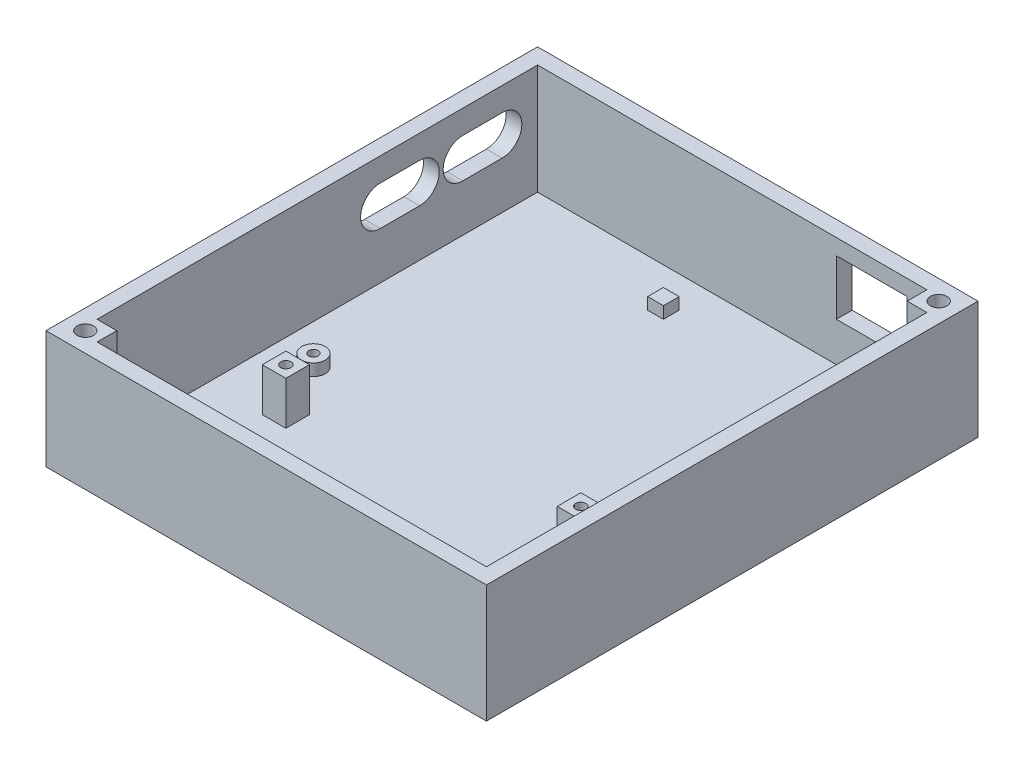
SolidWorks part; units mm, degrees
ref_plane "Front Plane" through (0, 0, 0) normal (0, 0, 1) x (1, 0, 0)
ref_plane "Top Plane" through (0, 0, 0) normal (0, 1, 0) x (1, 0, 0)
ref_plane "Right Plane" through (0, 0, 0) normal (1, 0, 0) x (0, 0, -1)
sketch "Sketch1" plane through (0, 0, 0) normal (0, 1, 0) x (1, 0, 0)
  line L1 (-56, -62.5) -> (56, -62.5)
  line L2 (-56, -62.5) -> (-56, 62.5)
  line L3 (-56, 62.5) -> (56, 62.5)
  line L4 (56, -62.5) -> (56, 62.5)
  line L5 (-56, -62.5) -> (56, 62.5) construction
  line L6 (-56, 62.5) -> (56, -62.5) construction
  point P0 (0, 0)
  dimension "D1" = 112
  dimension "D2" = 125
extrude "Boss-Extrude1" add sketch "Sketch1" along normal blind 2
sketch "Sketch2" plane through (0, 2, 0) normal (0, 1, 0) x (1, 0, 0)
  line L0 (-56, -62.5) -> (56, -62.5) construction
  line L1 (-12, 50.5) -> (-8, 50.5) construction
  line L2 (-12, 50.5) -> (-12, 46.5) construction
  line L3 (-12, 46.5) -> (-8, 46.5) construction
  line L4 (52, 53.5) -> (47, 53.5)
  line L5 (-8, 50.5) -> (-8, 46.5) construction
  line L6 (-56, 62.5) -> (-56, -62.5) construction
  line L7 (47, 53.5) -> (47, 58.5)
  line L8 (52, -58.5) -> (52, 58.5)
  line L9 (52, 58.5) -> (-52, 58.5)
  line L10 (-52, 58.5) -> (-52, -58.5)
  line L11 (-52, -58.5) -> (52, -58.5)
  line L12 (52, -58.5) -> (52, 53.5)
  line L13 (47, 58.5) -> (-52, 58.5)
  line L14 (-52, 58.5) -> (-52, -53.5)
  line L15 (-47, -58.5) -> (52, -58.5)
  line L16 (56, 62.5) -> (-56, 62.5) construction
  line L29 (-47, -58.5) -> (-47, -53.5)
  line L30 (-47, -53.5) -> (-52, -53.5)
  line L31 (56, -62.5) -> (56, 62.5) construction
  circle A0 centre (-42, -8.5) radius 1.2 construction
  circle A1 centre (38, -8.5) radius 1.2 construction
  circle A2 centre (-51, -57.5) radius 2.1
  circle A3 centre (51, 57.5) radius 2.1
  line M12 (56, -62.5) -> (56, 62.5)
  line M13 (56, 62.5) -> (-56, 62.5)
  line M14 (-56, 62.5) -> (-56, -62.5)
  line M15 (-56, -62.5) -> (56, -62.5)
  dimension "D1" = 2.4
  dimension "D13" = 4.2
  dimension "D15" = 4.2
  dimension "D18" = 5
  dimension "D2" = 80
  dimension "D3" = 5
  dimension "D5" = 8
  dimension "D6" = 62
  dimension "D7" = 5
  dimension "D8" = 14
  dimension "D9" = 4
  dimension "D10" = 4
  dimension "D11" = 40
  dimension "D12" = 5
  dimension "D14" = 5
  dimension "D16" = 5
  dimension "D17" = 5
  dimension "D4" = 4
extrude "Boss-Extrude2" add sketch "Sketch2" along normal blind 10 contours A0 | A1 | A3 A2 L29 L30 L14 L13 L7 L4 L12 L15 M15 M12 M13 M14 region at (48.9478, 2, -55.4478) region at (-48.9478, 2, 55.4478) region at (0, 2, 60.8216)
sketch "Sketch3" plane through (0, 2, 0) normal (0, 1, 0) x (1, 0, 0)
  line L0 (-32, -50.5) -> (-32, -25.5) construction
  line L1 (-35, -53.5) -> (40, -53.5) construction
  line L2 (-35, -53.5) -> (-35, -22.5) construction
  line L3 (-35, -22.5) -> (40, -22.5) construction
  line L4 (40, -53.5) -> (40, -22.5) construction
  line L5 (-32, -25.5) -> (37, -25.5) construction
  line L6 (37, -50.5) -> (37, -25.5) construction
  line L7 (-32, -50.5) -> (37, -50.5) construction
  line L8 (-38, -19.5) -> (43, -19.5)
  line L9 (43, -56.5) -> (43, -19.5)
  line L10 (-38, -56.5) -> (43, -56.5)
  line L11 (-38, -56.5) -> (-38, -19.5)
  line L12 (-47, -58.5) -> (52, -58.5) construction
  line L13 (-47, -58.5) -> (52, -58.5) construction
  line L14 (-32, -25.5) -> (-38, -25.5)
  line L15 (-32, -50.5) -> (-38, -50.5)
  line L16 (37, -25.5) -> (43, -25.5)
  line L17 (37, -50.5) -> (43, -50.5)
  line L18 (37, -25.5) -> (37, -19.5)
  line L19 (37, -50.5) -> (37, -56.5)
  line L20 (-32, -50.5) -> (-32, -56.5)
  line L21 (-32, -19.5) -> (-32, -25.5)
  circle A0 centre (-35, -22.5) radius 1.3
  circle A1 centre (40, -22.5) radius 1.3
  circle A2 centre (40, -53.5) radius 1.3
  circle A3 centre (-35, -53.5) radius 1.3
  point P17 (2.5, -22.5)
  point P19 (2.5, -58.5)
  dimension "D3" = 2.6
  dimension "D4" = 75
  dimension "D5" = 31
  dimension "D6" = 5
  dimension "D1" = 3
  dimension "D2" = 3
extrude "Boss-Extrude3" add sketch "Sketch3" along normal blind 11 contours L20 L15 L11 L10 A3 | L21 L8 L11 L14 A0 | L18 L16 L9 L8 A1 | L17 L19 L10 L9 A2 region at (-35, 2, 19.5849) region at (40, 2, 19.5849) region at (-35, 2, 50.5849) region at (42.9151, 2, 53.5)
sketch "Sketch5" plane through (0, 2, 0) normal (0, 1, 0) x (1, 0, 0)
  line L0 (-8, 50.5) -> (-8, 46.5) construction
  line L1 (-12, 50.5) -> (-8, 50.5) construction
  line L2 (-12, 50.5) -> (-12, 46.5) construction
  line L3 (-12, 46.5) -> (-8, 46.5) construction
  line L4 (-8, 50.5) -> (-8, 46.5)
  line L5 (-12, 50.5) -> (-8, 50.5)
  line L6 (-12, 50.5) -> (-12, 46.5)
  line L7 (-12, 46.5) -> (-8, 46.5)
  circle A0 centre (-42, -8.5) radius 3
  circle A1 centre (38, -8.5) radius 3
  circle A2 centre (38, -8.5) radius 1.2 construction
  circle A3 centre (38, -8.5) radius 1.2
  circle A4 centre (-42, -8.5) radius 1.2 construction
  circle A5 centre (-42, -8.5) radius 1.2
  dimension "D1" = 6
extrude "Boss-Extrude4" add sketch "Sketch5" along normal blind 3
sketch "Sketch6" plane through (0, 13, 0) normal (0, 1, 0) x (1, 0, 0)
  line L4 (-32, -56.5) -> (-32, -50.5)
  line L5 (-32, -50.5) -> (-38, -50.5)
  line L6 (-38, -50.5) -> (-38, -56.5)
  line L7 (-38, -56.5) -> (-32, -56.5)
  line L8 (-32, -56.5) -> (-32, -50.5)
  line L9 (-32, -50.5) -> (-38, -50.5)
  line L10 (-38, -50.5) -> (-38, -56.5)
  line L11 (-38, -56.5) -> (-32, -56.5)
  line L12 (37, -19.5) -> (37, -25.5)
  line L13 (37, -25.5) -> (43, -25.5)
  line L14 (43, -25.5) -> (43, -19.5)
  line L15 (43, -19.5) -> (37, -19.5)
  line L16 (37, -19.5) -> (37, -25.5)
  line L17 (37, -25.5) -> (43, -25.5)
  line L18 (43, -25.5) -> (43, -19.5)
  line L19 (43, -19.5) -> (37, -19.5)
  line L20 (43, -50.5) -> (37, -50.5)
  line L21 (37, -50.5) -> (37, -56.5)
  line L22 (37, -56.5) -> (43, -56.5)
  line L23 (43, -56.5) -> (43, -50.5)
  line L24 (43, -50.5) -> (37, -50.5)
  line L25 (37, -50.5) -> (37, -56.5)
  line L26 (37, -56.5) -> (43, -56.5)
  line L27 (43, -56.5) -> (43, -50.5)
  circle A0 centre (40, -53.5) radius 1.3 construction
  circle A1 centre (40, -22.5) radius 1.3
  circle A2 centre (40, -22.5) radius 1.3
  circle A3 centre (-35, -53.5) radius 1.3 construction
  circle A4 centre (40, -53.5) radius 1.3
  circle A5 centre (-35, -53.5) radius 1.3
  dimension "D1" = 0
  dimension "D2" = 0
  dimension "D3" = 0
  dimension "D4" = 0
extrude "Boss-Extrude5" add sketch "Sketch6" along normal blind 6.3
sketch "Sketch7" plane through (0, 12, 0) normal (0, 1, 0) x (1, 0, 0)
  line L4 (-56, -62.5) -> (56, -62.5)
  line L5 (56, -62.5) -> (56, 62.5)
  line L6 (56, 62.5) -> (-56, 62.5)
  line L7 (-56, 62.5) -> (-56, -62.5)
  line L8 (-56, -62.5) -> (56, -62.5)
  line L9 (56, -62.5) -> (56, 62.5)
  line L10 (56, 62.5) -> (-56, 62.5)
  line L11 (-56, 62.5) -> (-56, -62.5)
  circle M5 centre (51, 57.5) radius 2.1
  line M6 (47, 53.5) -> (52, 53.5)
  line M7 (52, 53.5) -> (52, -58.5)
  line M13 (52, 53.5) -> (52, -58.5)
  line M14 (52, -58.5) -> (-47, -58.5)
  line M15 (-47, -58.5) -> (-47, -53.5)
  line M16 (-47, -53.5) -> (-52, -53.5)
  line M17 (-52, -53.5) -> (-52, 58.5)
  line M18 (-52, 58.5) -> (47, 58.5)
  line M19 (47, 58.5) -> (47, 53.5)
  circle M22 centre (-51, -57.5) radius 2.1
  line M23 (-56, -62.5) -> (56, -62.5)
  line M24 (56, -62.5) -> (56, 62.5)
  line M25 (56, 62.5) -> (-56, 62.5)
  line M26 (-56, 62.5) -> (-56, -62.5)
  dimension "D1" = 0
extrude "Boss-Extrude6" add sketch "Sketch7" along normal blind 18 contours M26 M23 M24 M25 M22 M5 M7 M13 M14 M15 M16 M17 M18 M19 M6 region at (-54.3216, 12, 0)
sketch "Sketch9" plane through (-56, 0, 0) normal (-1, 0, 0) x (0, 0, 1)
  line L0 (-49.5, 19) -> (-39.5, 19) construction
  line L1 (-49.5, 24) -> (-39.5, 24)
  line L2 (-49.5, 14) -> (-39.5, 14)
  line L3 (-28.5, 19) -> (-18.5, 19) construction
  line L4 (-28.5, 24) -> (-18.5, 24)
  line L5 (-28.5, 14) -> (-18.5, 14)
  line L9 (-62.5, 30) -> (62.5, 30) construction
  line L10 (-62.5, 30) -> (-62.5, 0) construction
  arc A0 (-49.5, 24) -> (-49.5, 14) centre (-49.5, 19) ccw
  arc A1 (-39.5, 14) -> (-39.5, 24) centre (-39.5, 19) ccw
  arc A2 (-28.5, 24) -> (-28.5, 14) centre (-28.5, 19) ccw
  arc A3 (-18.5, 14) -> (-18.5, 24) centre (-18.5, 19) ccw
  point P2 (-44.5, 19)
  point P8 (-23.5, 19)
  point P23 (-34.5, 19)
  point P24 (-54.5, 19)
  dimension "D2" = 5
  dimension "D1" = 11
  dimension "D3" = 20
  dimension "D4" = 13
  dimension "D5" = 34
extrude "Cut-Extrude1" cut sketch "Sketch9" against normal up to next
sketch "Sketch10" plane through (0, 0, -62.5) normal (0, 0, -1) x (-1, 0, 0)
  line L3 (-24, 12) -> (-42, 12)
  line L5 (-56, 30) -> (-56, 0) construction
  line L6 (-42, 26) -> (-24, 26)
  line L7 (-42, 26) -> (-42, 12)
  line L8 (-24, 12) -> (-24, 26)
  line L9 (-56, 30) -> (56, 30) construction
  line L10 (-56, 0) -> (56, 0) construction
  point P8 (-33, 12)
  dimension "D1" = 14
  dimension "D2" = 23
  dimension "D3" = 18
  dimension "D4" = 4
  dimension "D5" = 12
extrude "Cut-Extrude2" cut sketch "Sketch10" against normal up to next
